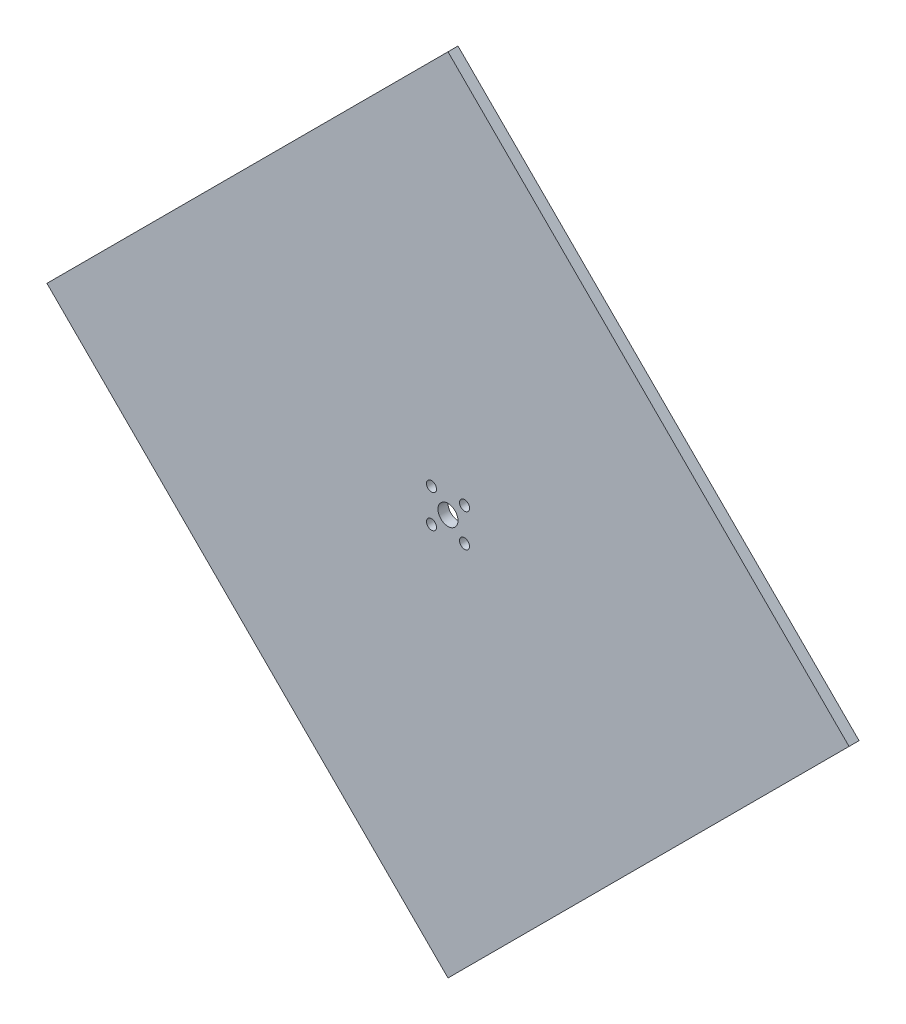
SolidWorks part; units mm, degrees
ref_plane "前视基准面" through (0, 0, 0) normal (0, 0, 1) x (1, 0, 0)
ref_plane "上视基准面" through (0, 0, 0) normal (0, 1, 0) x (1, 0, 0)
ref_plane "右视基准面" through (0, 0, 0) normal (1, 0, 0) x (0, 0, -1)
sketch "草图1" plane through (0, 0, 0) normal (0, 0, 1) x (1, 0, 0)
  line L1 (85, -85) -> (-85, -85)
  line L2 (85, -85) -> (85, 85)
  line L3 (85, 85) -> (-85, 85)
  line L4 (-85, -85) -> (-85, 85)
  line L5 (85, -85) -> (-85, 85) construction
  line L6 (85, 85) -> (-85, -85) construction
  point P0 (0, 0)
  dimension "D1" = 170
  dimension "D2" = 170
extrude "凸台-拉伸1" add sketch "草图1" along normal blind 3
sketch "草图3" plane through (0, 0, 0) normal (0, 0, -1) x (-1, 0, 0)
  line L1 (4.95, -4.95) -> (-4.95, -4.95) construction
  line L2 (4.95, -4.95) -> (4.95, 4.95) construction
  line L3 (4.95, 4.95) -> (-4.95, 4.95) construction
  line L4 (-4.95, -4.95) -> (-4.95, 4.95) construction
  line L5 (4.95, -4.95) -> (-4.95, 4.95) construction
  line L6 (4.95, 4.95) -> (-4.95, -4.95) construction
  circle A0 centre (0, 0) radius 3
  circle A1 centre (4.95, 4.95) radius 1.5
  circle A2 centre (-4.95, 4.95) radius 1.5
  circle A3 centre (-4.95, -4.95) radius 1.5
  circle A4 centre (4.95, -4.95) radius 1.5
  point P0 (0, 0)
  dimension "D1" = 6
  dimension "D2" = 3
  dimension "D3" = 3
  dimension "D4" = 3
  dimension "D5" = 3
  dimension "D6" = 9.9
  dimension "D7" = 9.9
extrude "切除-拉伸1" cut sketch "草图3" against normal through all
fillet "圆角1" radius 2 4 edges at (85, -85, 1.5) (85, 85, 1.5) (-85, -85, 1.5) (-85, 85, 1.5)
sketch "草图4" plane through (0, 0, 0) normal (0, 0, -1) x (-1, 0, 0)
  line L0 (0, 0) -> (22.2376, 22.2376) construction
  line L1 (60.1041, -60.1041) -> (-60.1041, 60.1041)
  line L2 (35.2082, -85) -> (85, -35.2082)
  line L3 (-85, 35.2082) -> (-35.2082, 85)
  line L4 (-85, 83) -> (-85, -83)
  line L5 (-83, -85) -> (83, -85)
  line L6 (85, -83) -> (85, 83)
  line L7 (83, 85) -> (-83, 85)
  line L8 (-85, 83) -> (-85, -83)
  line L9 (-83, -85) -> (83, -85)
  line L10 (85, -83) -> (85, 83)
  line L11 (83, 85) -> (-83, 85)
  line L12 (-60.1041, -60.1041) -> (60.1041, 60.1041)
  line L13 (-60.1041, -60.1041) -> (-85, -36.1123)
  line L14 (-60.1041, -60.1041) -> (-34.2699, -85)
  line L15 (60.1041, 60.1041) -> (85, 34.2699)
  line L16 (60.1041, 60.1041) -> (36.1123, 85)
  arc A4 (-85, -83) -> (-83, -85) centre (-83, -83) ccw
  arc A5 (83, -85) -> (85, -83) centre (83, -83) ccw
  arc A6 (85, 83) -> (83, 85) centre (83, 83) ccw
  arc A7 (-83, 85) -> (-85, 83) centre (-83, 83) ccw
  arc A8 (-85, -83) -> (-83, -85) centre (-83, -83) ccw
  arc A9 (83, -85) -> (85, -83) centre (83, -83) ccw
  arc A10 (85, 83) -> (83, 85) centre (83, 83) ccw
  arc A11 (-83, 85) -> (-85, 83) centre (-83, 83) ccw
  line M18 (-85, 83) -> (-85, -83)
  line M20 (-83, -85) -> (83, -85)
  arc M21 (83, -85) -> (85, -83) centre (83, -83) ccw
  line M22 (85, -83) -> (85, 83)
  line M24 (83, 85) -> (-83, 85)
  arc M25 (-83, 85) -> (-85, 83) centre (-83, 83) ccw
  dimension "D2" = 85
  dimension "D3" = 85
  dimension "D1" = 0
extrude "切除-拉伸2" cut sketch "草图4" against normal blind 10 contours L3 M18 M24 M25 | L2 M20 M21 M22 region at (-68.3915, -68.3915, 0) region at (68.3915, 68.3915, 0)
sketch "草图5" plane through (0, 0, 0) normal (0, 0, -1) x (-1, 0, 0)
  line L0 (-35.2082, 85) -> (24.3101, 144.5183)
  line L1 (24.3101, 144.5183) -> (144.5183, 24.3101)
  line L2 (0, 0) -> (-60.1041, 60.1041) construction
  line L3 (-85, 35.2082) -> (-35.2082, 85) construction
  line L4 (0, 0) -> (84.4142, 84.4142) construction
  line L5 (-85, -83) -> (-85, 35.2082)
  line L6 (-144.5183, -24.3101) -> (-24.3101, -144.5183)
  line L7 (-85, 35.2082) -> (-144.5183, -24.3101)
  line L8 (85, -35.2082) -> (144.5183, 24.3101)
  line L9 (35.2082, -85) -> (-24.3101, -144.5183)
  line L11 (83, 85) -> (-35.2082, 85)
  line L12 (-35.2082, 85) -> (-85, 35.2082)
  line L13 (-85, 35.2082) -> (-85, -83)
  line L14 (-83, -85) -> (35.2082, -85)
  line L15 (35.2082, -85) -> (85, -35.2082)
  line L16 (85, -35.2082) -> (85, 83)
  line L17 (83, 85) -> (-35.2082, 85)
  line L18 (-35.2082, 85) -> (-85, 35.2082)
  line L19 (-85, 35.2082) -> (-85, -83)
  line L20 (-83, -85) -> (35.2082, -85)
  line L21 (35.2082, -85) -> (85, -35.2082)
  line L22 (85, -35.2082) -> (85, 83)
  arc A0 (85, 83) -> (83, 85) centre (83, 83) ccw construction
  arc A3 (-85, -83) -> (-83, -85) centre (-83, -83) ccw
  arc A4 (85, 83) -> (83, 85) centre (83, 83) ccw
  arc A5 (-85, -83) -> (-83, -85) centre (-83, -83) ccw
  arc A6 (85, 83) -> (83, 85) centre (83, 83) ccw
  point P25 (-84.4142, -84.4142)
  dimension "D1" = 0
sketch "草图6" plane through (0, 0, 0) normal (0, 0, -1) x (-1, 0, 0)
  line L0 (-60.1041, -60.1041) -> (60.1041, 60.1041)
  line L1 (0, 0) -> (84.4142, 84.4142) construction
  line L2 (0, 0) -> (-32.158, 32.158)
  line L3 (0, 0) -> (-60.1041, 60.1041) construction
  line L4 (60.1041, 60.1041) -> (35.2082, 85)
  line L5 (60.1041, 60.1041) -> (85, 35.2082)
  line L6 (83, 85) -> (-35.2082, 85)
  line L7 (-35.2082, 85) -> (-85, 35.2082)
  line L8 (-85, 35.2082) -> (-85, -83)
  line L9 (-83, -85) -> (35.2082, -85)
  line L10 (35.2082, -85) -> (85, -35.2082)
  line L11 (85, -35.2082) -> (85, 83)
  line L12 (83, 85) -> (-35.2082, 85)
  line L13 (-35.2082, 85) -> (-85, 35.2082)
  line L14 (-85, 35.2082) -> (-85, -83)
  line L15 (-83, -85) -> (35.2082, -85)
  line L16 (35.2082, -85) -> (85, -35.2082)
  line L17 (85, -35.2082) -> (85, 83)
  line L18 (-60.1041, -60.1041) -> (-35.2082, -85)
  line L19 (-60.1041, -60.1041) -> (-85, -35.2082)
  arc A2 (-85, -83) -> (-83, -85) centre (-83, -83) ccw
  arc A3 (85, 83) -> (83, 85) centre (83, 83) ccw
  arc A4 (-85, -83) -> (-83, -85) centre (-83, -83) ccw
  arc A5 (85, 83) -> (83, 85) centre (83, 83) ccw
  line M18 (83, 85) -> (-35.2082, 85)
  arc M21 (-85, -83) -> (-83, -85) centre (-83, -83) ccw
  line M22 (-83, -85) -> (35.2082, -85)
  line M24 (85, -35.2082) -> (85, 83)
  arc M25 (85, 83) -> (83, 85) centre (83, 83) ccw
  dimension "D2" = 85
  dimension "D1" = 0
extrude "切除-拉伸3" cut sketch "草图6" against normal blind 3 contours L18 L19 L14 M21 M22 | L4 L5 M24 M25 M18 region at (68.3915, -68.3915, 0) region at (-68.3915, 68.3915, 0)
sketch "草图7" plane through (0, 0, 0) normal (0, 0, -1) x (-1, 0, 0)
  line L0 (-120.2082, 0) -> (0, 120.2082)
  line L1 (-35.2082, 85) -> (24.3101, 144.5183) construction
  line L2 (0, 120.2082) -> (35.2082, 85)
  line L3 (0, 0) -> (-21.4242, 21.4242)
  line L4 (0, 0) -> (-60.1041, 60.1041) construction
  line L5 (0, 0) -> (24.2164, 24.2164)
  line L6 (0, 0) -> (84.4142, 84.4142) construction
  line L7 (-120.2082, 0) -> (-85, -35.2082)
  line L8 (-85, -35.2082) -> (-35.2082, -85)
  line L9 (-35.2082, -85) -> (35.2082, -85)
  line L10 (35.2082, -85) -> (85, -35.2082)
  line L11 (85, -35.2082) -> (85, 35.2082)
  line L12 (85, 35.2082) -> (35.2082, 85)
  line L13 (35.2082, 85) -> (-35.2082, 85)
  line L14 (-35.2082, 85) -> (-85, 35.2082)
  line L15 (-85, 35.2082) -> (-85, -35.2082)
  line L16 (-85, -35.2082) -> (-35.2082, -85)
  line L17 (-35.2082, -85) -> (35.2082, -85)
  line L18 (35.2082, -85) -> (85, -35.2082)
  line L19 (85, -35.2082) -> (85, 35.2082)
  line L20 (85, 35.2082) -> (35.2082, 85)
  line L21 (35.2082, 85) -> (-35.2082, 85)
  line L22 (-35.2082, 85) -> (-85, 35.2082)
  line L23 (-85, 35.2082) -> (-85, -35.2082)
  line L24 (85, 35.2082) -> (85, -35.2082)
  line L25 (120.2082, 0) -> (85, 35.2082)
  line L26 (35.2082, -85) -> (-35.2082, -85)
  line L27 (0, -120.2082) -> (-35.2082, -85)
  line L28 (0, -120.2082) -> (120.2082, 0)
  point P22 (-60.1041, 60.1041)
  line M19 (-35.2082, -85) -> (35.2082, -85)
  line M21 (85, -35.2082) -> (85, 35.2082)
  line M23 (35.2082, 85) -> (-35.2082, 85)
  line M25 (-85, 35.2082) -> (-85, -35.2082)
  dimension "D1" = 0
extrude "凸台-拉伸4" add sketch "草图7" against normal blind 3 contours L0 L7 M25 | L2 L0 M23 | L27 L28 M19 | L28 L25 M21 region at (96.7361, 0, 0) region at (0, 96.7361, 0) region at (0, -96.7361, 0) region at (-96.7361, 0, 0)
